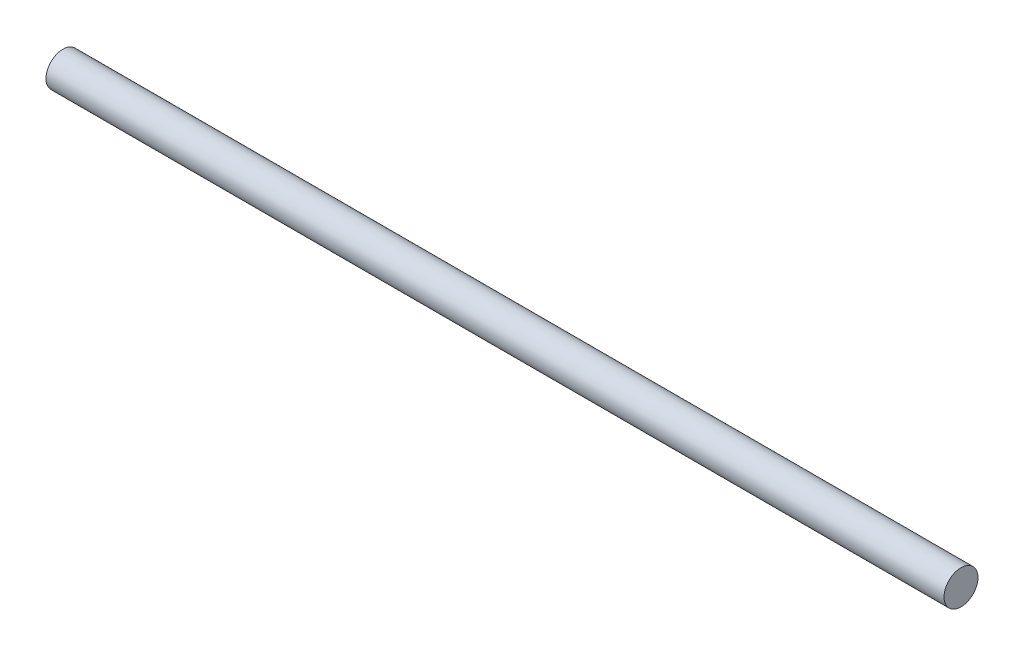
SolidWorks part; units mm, degrees
material "Copper"
ref_plane "Front Plane" through (0, 0, 0) normal (0, 0, 1) x (1, 0, 0)
ref_plane "Top Plane" through (0, 0, 0) normal (0, 1, 0) x (1, 0, 0)
ref_plane "Right Plane" through (0, 0, 0) normal (1, 0, 0) x (0, 0, -1)
sketch "Sketch1" plane through (0, 0, 0) normal (1, 0, 0) x (0, 0, -1)
  circle A0 centre (0, 0) radius 0.2921
  dimension "D1" = 0.5842
extrude "Boss-Extrude1" add sketch "Sketch1" along normal blind 15.45
